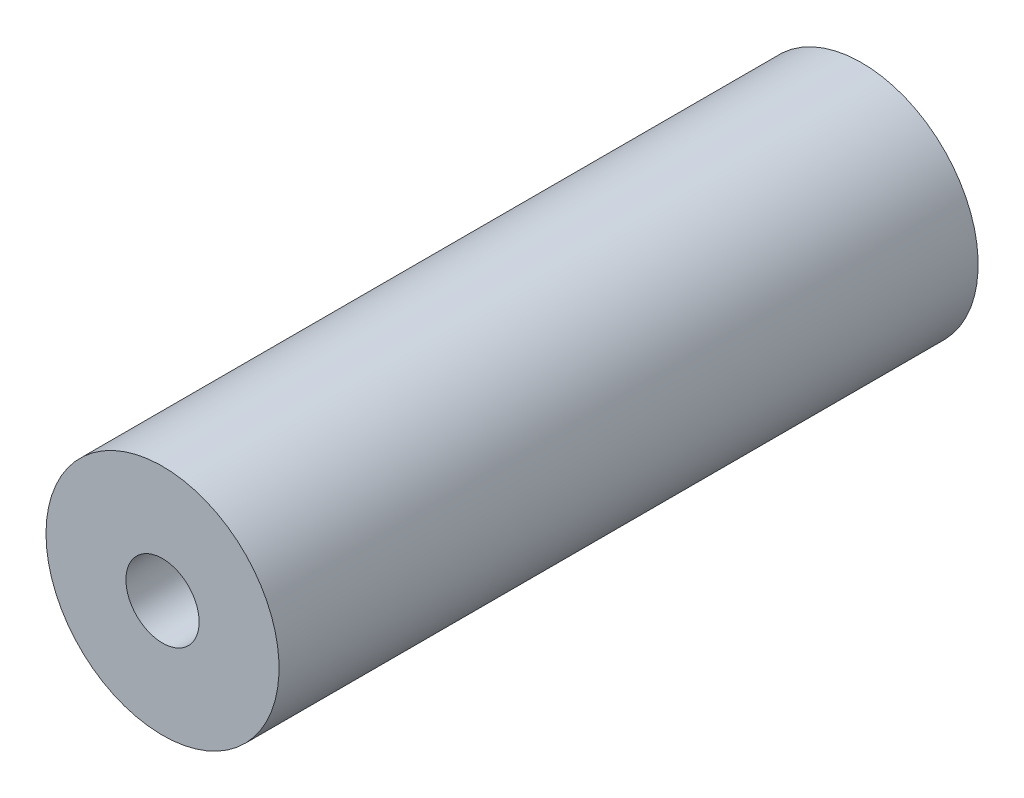
SolidWorks part; units mm, degrees
ref_plane "Front Plane" through (0, 0, 0) normal (0, 0, 1) x (1, 0, 0)
ref_plane "Top Plane" through (0, 0, 0) normal (0, 1, 0) x (1, 0, 0)
ref_plane "Right Plane" through (0, 0, 0) normal (1, 0, 0) x (0, 0, -1)
sketch "Sketch2" plane through (0, 0, 0) normal (0, 0, 1) x (1, 0, 0)
  circle A0 centre (0, 0) radius 3.5
extrude "Boss-Extrude1" add sketch "Sketch2" along normal blind 21
sketch "Sketch4" plane through (0, 0, 0) normal (0, 0, -1) x (-1, 0, 0)
  line L1 (-2.325, 2.325) -> (2.325, 2.325)
  line L2 (-2.325, 2.325) -> (-2.325, -2.325)
  line L3 (-2.325, -2.325) -> (2.325, -2.325)
  line L4 (2.325, 2.325) -> (2.325, -2.325)
  line L5 (-2.325, 2.325) -> (2.325, -2.325) construction
  line L6 (-2.325, -2.325) -> (2.325, 2.325) construction
  point P0 (0, 0)
  dimension "D1" = 4.65
  dimension "D2" = 4.65
sketch "Sketch7" plane through (0, 0, 21) normal (0, 0, 1) x (1, 0, 0)
  circle A0 centre (0, 0) radius 1.1
extrude "Cut-Extrude2" cut sketch "Sketch7" against normal blind 6
extrude "Cut-Extrude5" cut sketch "Sketch4" against normal blind 10.2
ref_plane "Plane1" through (0, 0, 11.5) normal (0, 0, -1) x (-1, 0, 0)
sketch "Sketch14" plane through (0, 0, 11.5) normal (0, 0, -1) x (-1, 0, 0)
  circle A0 centre (0, 0) radius 3.5
